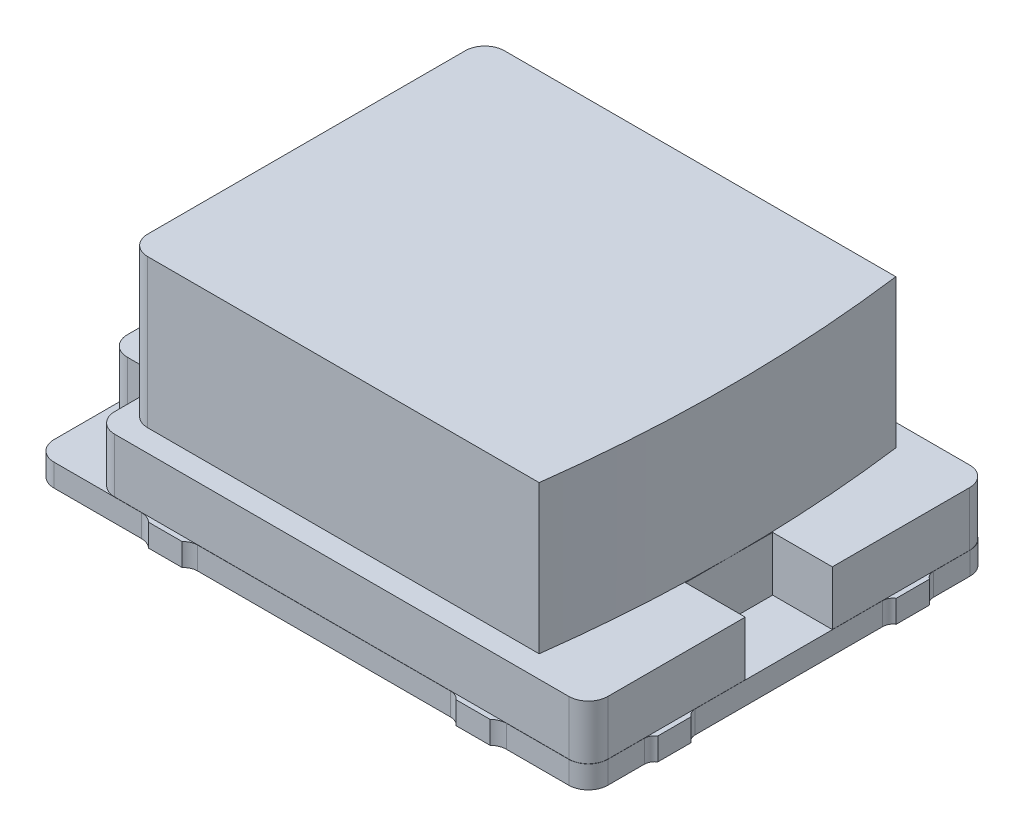
SolidWorks part; units mm, degrees
ref_plane "Front Plane" through (0, 0, 0) normal (0, 0, 1) x (1, 0, 0)
ref_plane "Top Plane" through (0, 0, 0) normal (0, 1, 0) x (1, 0, 0)
ref_plane "Right Plane" through (0, 0, 0) normal (1, 0, 0) x (0, 0, -1)
sketch "Sketch1" plane through (0, 0, 0) normal (0, 1, 0) x (1, 0, 0)
  line L1 (-28.3, -20.5) -> (28.3, -20.5)
  line L2 (-28.3, -20.5) -> (-28.3, 20.5)
  line L3 (-28.3, 20.5) -> (28.3, 20.5)
  line L4 (28.3, -20.5) -> (28.3, 20.5)
  line L5 (-28.3, -20.5) -> (28.3, 20.5) construction
  line L6 (-28.3, 20.5) -> (28.3, -20.5) construction
  point P0 (0, 0)
extrude "Boss-Extrude1" add sketch "Sketch1" along normal blind 2.3
sketch "Sketch2" plane through (0, 2.3, 0) normal (0, 1, 0) x (1, 0, 0)
  line L0 (0, 0) -> (0, 12.239) construction
  line L1 (28.285, -20.48) -> (-28.285, -20.48)
  line L2 (28.285, -20.48) -> (28.285, 20.48)
  line L3 (28.285, 20.48) -> (-28.285, 20.48)
  line L4 (-28.285, -20.48) -> (-28.285, 20.48)
  line L5 (28.285, -20.48) -> (-28.285, 20.48) construction
  line L6 (28.285, 20.48) -> (-28.285, -20.48) construction
  line L7 (0, 0) -> (13.1918, 0) construction
  line L8 (22.185, 0) -> (28.285, 0) construction
  line L9 (-28.285, 13.02) -> (-22.125, 13.02)
  line L10 (-22.125, 13.02) -> (-22.125, 20.48)
  line L11 (28.285, 4.45) -> (22.185, 4.45)
  line L12 (28.285, 4.45) -> (28.285, -4.45)
  line L13 (28.285, -4.45) -> (22.185, -4.45)
  line L14 (-28.285, -13.02) -> (-22.125, -13.02)
  line L15 (-22.125, -13.02) -> (-22.125, -20.48)
  line L16 (22.185, 4.45) -> (22.185, -4.45)
  line L17 (-28.285, 13.02) -> (-28.285, 20.48)
  line L18 (-28.285, -13.02) -> (-28.285, -20.48)
  point P0 (0, 0)
extrude "Boss-Extrude2" add sketch "Sketch2" along normal blind 5.55 contours L16 L11 L2 L3 L10 L9 L4 L14 L15 L1 L13 region at (0.436, 2.3, 0)
sketch "Sketch3" plane through (0, 7.85, 0) normal (0, 1, 0) x (1, 0, 0)
  line L1 (-19, -18.225) -> (21, -18.225)
  line L2 (-21, -16.225) -> (-21, 16.225)
  line L3 (-19, 18.225) -> (21, 18.225)
  line L5 (-21, -18.225) -> (21, 18.225) construction
  line L6 (-21, 18.225) -> (21, -18.225) construction
  arc A0 (21, -18.225) -> (21, 18.225) centre (-118.5554, 0) ccw
  arc A1 (-21, 16.225) -> (-19, 18.225) centre (-19, 16.225) cw
  arc A2 (-21, -16.225) -> (-19, -18.225) centre (-19, -16.225) ccw
  point P0 (0, 0)
  dimension "D1" = 2
extrude "Boss-Extrude3" add sketch "Sketch3" along normal blind 15.15
fillet "Fillet1" radius 2 12 edges at (-22.125, 5.075, -13.02) (-28.285, 5.075, -13.02) (-22.125, 5.075, -20.48) (-28.285, 5.075, 13.02) (-22.125, 5.075, 13.02) (-22.125, 5.075, 20.48) (28.3, 1.15, 20.5) (28.285, 5.075, 20.48) (28.3, 1.15, -20.5) (28.285, 5.075, -20.48) (-28.3, 1.15, 20.5) (-28.3, 1.15, -20.5)
sketch "Sketch4" plane through (0, 0, 0) normal (0, 1, 0) x (1, 0, 0)
  line L0 (28.785, 12.18) -> (29.8277, 12.18) construction
  line L1 (28.285, 4.45) -> (28.285, 18.48) construction
  line L4 (28.285, 13.88) -> (28.285, 10.48)
  line L6 (28.785, 13.88) -> (28.785, 10.48)
  line L7 (28.3, -18.5) -> (28.3, 18.5) construction
  line L8 (28.3, 14.7724) -> (28.3, 9.5876)
  line L9 (28.3, 0) -> (32.8587, 0) construction
  line L10 (28.785, -13.88) -> (28.785, -10.48)
  line L11 (28.3, -14.7724) -> (28.3, -9.5876)
  arc A0 (28.3, 14.7724) -> (28.785, 13.88) centre (29.3634, 14.7724) ccw
  arc A1 (28.3, 9.5876) -> (28.785, 10.48) centre (29.3634, 9.5876) cw
  arc A2 (28.3, -14.7724) -> (28.785, -13.88) centre (29.3634, -14.7724) cw
  arc A3 (28.3, -9.5876) -> (28.785, -10.48) centre (29.3634, -9.5876) ccw
  dimension "D2" = 3.4
extrude "Boss-Extrude5" add sketch "Sketch4" along direction (0, -1, 0) on the side of the normal up to surface (2.3 mm away) contours L8 A1 L6 A0 | A3 L11 A2 L10 region at (28.5284, 0, -12.18) region at (28.5284, 0, 12.18) up to face at (-3.803, 2.3, 0)
sketch "Sketch5" plane through (29.4347, 0, -17.005) normal (0, 1, 0) x (0, 0, -1)
  line L2 (-37.505, 43.871) -> (-37.99, 43.871) construction
  line L3 (3.495, 3.1347) -> (3.495, 55.7347) construction
  line L4 (3.495, 9.6293) -> (3.495, 9.4863)
  line L5 (-37.505, 12.4285) -> (-37.99, 12.4285) construction
  line L6 (3.98, 14.1497) -> (3.98, 10.7072)
  line L8 (3.495, 15.2277) -> (3.495, 9.6293)
  line L9 (-12.555, 1.1497) -> (1.475, 1.1497) construction
  line L10 (3.495, 12.4285) -> (3.98, 12.4285) construction
  line L11 (-37.505, 46.8132) -> (-37.505, 46.6702)
  line L12 (3.495, 43.871) -> (3.98, 43.871) construction
  line L13 (3.495, 41.0718) -> (3.495, 46.6702)
  line L14 (3.98, 42.1497) -> (3.98, 45.5922)
  line L15 (-17.005, 57.7197) -> (-17.005, 64.4158) construction
  line L16 (-28.025, 57.7197) -> (-5.985, 57.7197) construction
  line L17 (3.495, 46.8132) -> (3.495, 46.6702)
  line L18 (-37.99, 42.1497) -> (-37.99, 45.5922)
  line L19 (-37.505, 41.0718) -> (-37.505, 46.6702)
  line L20 (-37.505, 15.2277) -> (-37.505, 9.6293)
  line L21 (-37.99, 14.1497) -> (-37.99, 10.7072)
  line L22 (-37.505, 9.6293) -> (-37.505, 9.4863)
  arc A2 (3.495, 15.2277) -> (3.98, 14.1497) centre (4.9354, 15.2277) ccw
  arc A3 (3.98, 10.7072) -> (3.495, 9.4863) centre (5.2744, 9.4863) ccw
  arc A4 (3.98, 45.5922) -> (3.495, 46.8132) centre (5.2744, 46.8132) cw
  arc A5 (3.495, 41.0718) -> (3.98, 42.1497) centre (4.9354, 41.0718) cw
  arc A6 (-37.505, 41.0718) -> (-37.99, 42.1497) centre (-38.9454, 41.0718) ccw
  arc A7 (-37.99, 45.5922) -> (-37.505, 46.8132) centre (-39.2844, 46.8132) ccw
  arc A8 (-37.99, 10.7072) -> (-37.505, 9.4863) centre (-39.2844, 9.4863) cw
  arc A9 (-37.505, 15.2277) -> (-37.99, 14.1497) centre (-38.9454, 15.2277) cw
  dimension "D4" = 0.485
  dimension "D2" = 13
  dimension "D5" = 0.485
extrude "Boss-Extrude6" add sketch "Sketch5" along normal up to surface (2.3 mm away) up to face at (-3.803, 2.3, 0)
